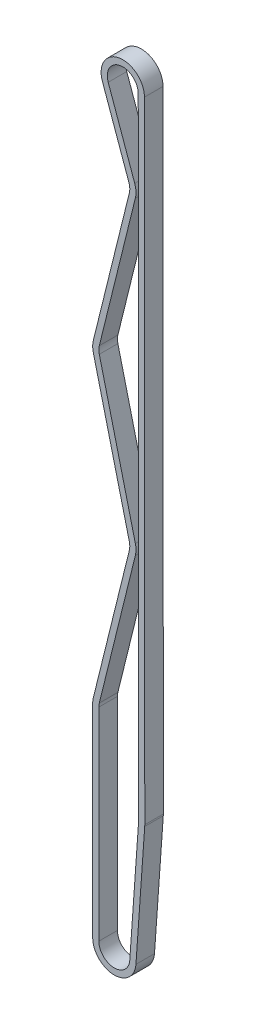
SolidWorks part; units mm, degrees
ref_plane "Front Plane" through (0, 0, 0) normal (0, 0, 1) x (1, 0, 0)
ref_plane "Top Plane" through (0, 0, 0) normal (0, 1, 0) x (1, 0, 0)
ref_plane "Right Plane" through (0, 0, 0) normal (1, 0, 0) x (0, 0, -1)
sketch "Sketch1" plane through (0, 0, 0) normal (0, 0, 1) x (1, 0, 0)
  line L0 (-5, 0) -> (-5, 65.5)
  line L5 (7.7288, 243.55) -> (7.8375, 40.0027)
  line L6 (7.825, 39.6462) -> (4.9875, -0.3538)
  line L7 (-4.8539, 66.7) -> (6.7954, 113.82)
  line L8 (-4.8539, 164.3) -> (6.7954, 117.18)
  line L9 (-4.8539, 166.7) -> (6.7954, 213.82)
  line L10 (-1.9802, 241.8691) -> (6.5926, 217.8533)
  line L11 (-3.8638, 241.1967) -> (4.709, 217.1809)
  line L12 (9.7287, 243.5505) -> (9.8375, 40.0037)
  line L13 (9.82, 39.5047) -> (6.9825, -0.4953)
  line L14 (-7, 0) -> (-7, 65.5)
  line L15 (-6.7954, 67.18) -> (4.8539, 114.3)
  line L16 (-6.7954, 163.82) -> (4.8539, 116.7)
  line L17 (-6.7954, 167.18) -> (4.8539, 214.3)
  circle A0 centre (2.7288, 243.55) radius 5 construction
  circle A1 centre (0, 215.5) radius 5 construction
  circle A2 centre (0, 165.5) radius 5 construction
  circle A3 centre (0, 115.5) radius 5 construction
  circle A4 centre (0, 65.5) radius 5 construction
  circle A5 centre (2.8375, 40) radius 5 construction
  circle A6 centre (0, 0) radius 5 construction
  circle A7 centre (2.7288, 243.55) radius 5 construction
  circle A8 centre (0, 215.5) radius 5 construction
  circle A9 centre (0, 165.5) radius 5 construction
  circle A10 centre (0, 115.5) radius 5 construction
  circle A11 centre (0, 65.5) radius 5 construction
  circle A12 centre (2.8375, 40) radius 5 construction
  circle A13 centre (0, 0) radius 5 construction
  arc A14 (4.9875, -0.3538) -> (-5, 0) centre (0, 0) cw
  arc A15 (7.825, 39.6462) -> (7.8375, 40.0027) centre (2.8375, 40) ccw
  arc A16 (-5, 65.5) -> (-4.8539, 66.7) centre (0, 65.5) cw
  arc A18 (-4.8539, 164.3) -> (-4.8539, 166.7) centre (0, 165.5) cw
  arc A20 (-1.9802, 241.8691) -> (7.7288, 243.55) centre (2.7288, 243.55) cw
  arc A21 (6.7954, 113.82) -> (6.7954, 117.18) centre (0, 115.5) ccw
  arc A22 (6.7954, 213.82) -> (6.5926, 217.8533) centre (0, 215.5) ccw
  arc A23 (4.8539, 214.3) -> (4.709, 217.1809) centre (0, 215.5) ccw
  arc A24 (-3.8638, 241.1967) -> (9.7287, 243.5505) centre (2.7288, 243.55) cw
  arc A25 (9.82, 39.5047) -> (9.8375, 40.0037) centre (2.8375, 40) ccw
  arc A26 (6.9825, -0.4953) -> (-7, 0) centre (0, 0) cw
  arc A27 (-7, 65.5) -> (-6.7954, 67.18) centre (0, 65.5) cw
  arc A28 (4.8539, 114.3) -> (4.8539, 116.7) centre (0, 115.5) ccw
  arc A29 (-6.7954, 163.82) -> (-6.7954, 167.18) centre (0, 165.5) cw
  point P63 (-4.8539, 67.0338)
  point P64 (-4.8539, 166.2067)
  dimension "D1" = 2
extrude "Boss-Extrude1" add sketch "Sketch1" along normal blind 6
